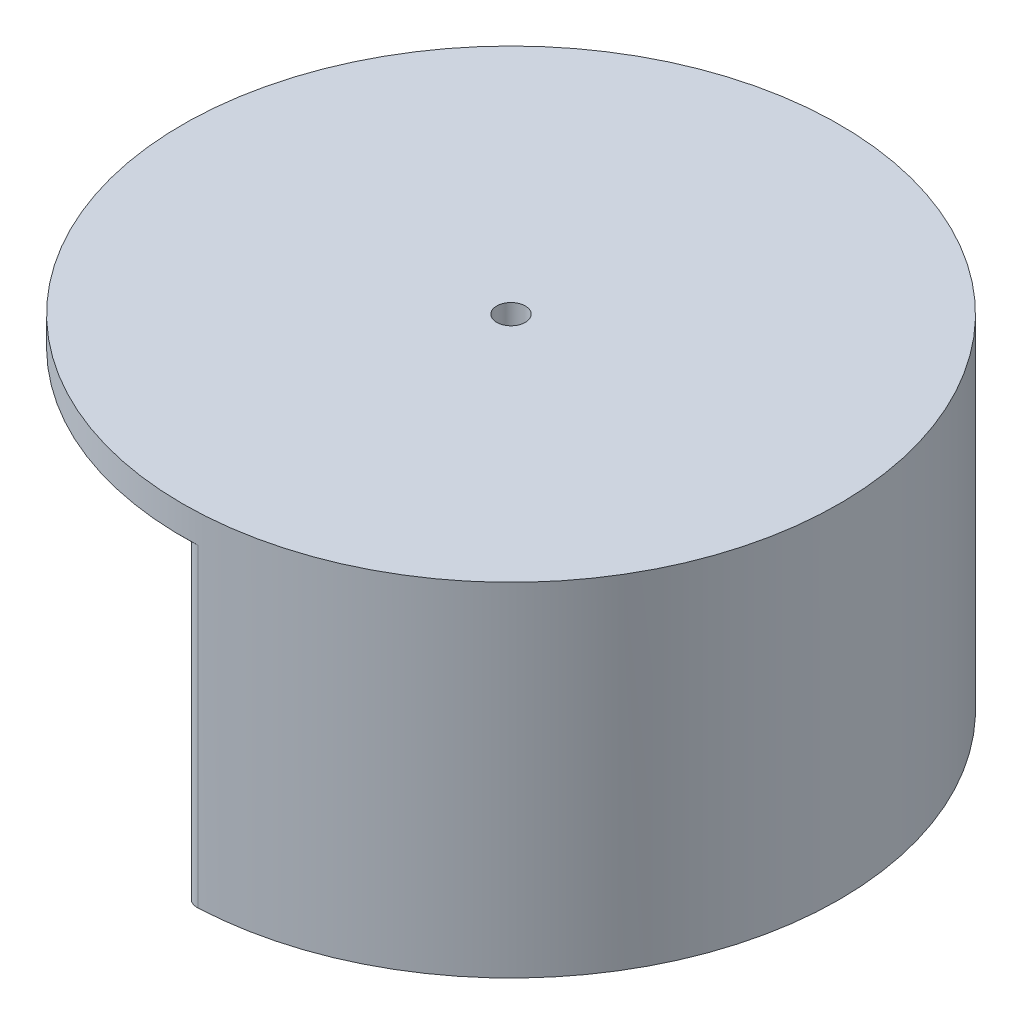
SolidWorks part; units mm, degrees
ref_plane "Front Plane" through (0, 0, 0) normal (0, 0, 1) x (1, 0, 0)
ref_plane "Top Plane" through (0, 0, 0) normal (0, 1, 0) x (1, 0, 0)
ref_plane "Right Plane" through (0, 0, 0) normal (1, 0, 0) x (0, 0, -1)
sketch "Sketch1" plane through (0, 0, 0) normal (0, 1, 0) x (1, 0, 0)
  circle A0 centre (0, 0) radius 23
  dimension "D1" = 46
extrude "Boss-Extrude1" add sketch "Sketch1" along normal blind 24
sketch "Sketch3" plane through (0, 0, 0) normal (1, 0, 0) x (0, 0, -1)
  line L0 (0, 0.5522) -> (-23, 22)
  line L3 (-23, 22) -> (0, 22) construction
  line L4 (0, 22) -> (0, 0.5522) construction
  line L6 (-23, 24) -> (-23, 0) construction
  line L7 (0, 0) -> (0, 24) construction
  line L8 (-23, 0) -> (23, 0) construction
  line L9 (23, 24) -> (-23, 24) construction
  line L10 (-23, 22) -> (-23, 0)
  line L11 (-23, 0) -> (0, 0)
  line L12 (0, 0) -> (0, 0.5522)
  dimension "D1" = 43
  dimension "D2" = 2
revolve "Cut-Revolve1" cut sketch "Sketch3" angle 180 about L4
sketch "Sketch4" plane through (0, 0, 0) normal (0, -1, 0) x (1, 0, 0)
  line L2 (2, 20.9045) -> (2, -20.9045)
  line L3 (2, 20.9045) -> (2, -20.9045)
  arc A2 (2, -20.9045) -> (2, 20.9045) centre (0, 0) ccw
  arc A3 (2, -20.9045) -> (2, 20.9045) centre (0, 0) ccw
  dimension "D1" = 2
extrude "Cut-Extrude2" cut sketch "Sketch4" against normal offset from surface (22 mm away) 2 up to face at (0, 24, 23)
sketch "Sketch5" plane through (0, 24, 0) normal (0, 1, 0) x (1, 0, 0)
  circle A0 centre (0, 0) radius 1
  dimension "D1" = 2
extrude "Cut-Extrude3" cut sketch "Sketch5" against normal through all
fillet "Fillet1" radius 1 6 edges at (0, 0.7423, -1) (0, 0.7423, 1) (1, 0, 0) (-1, 1.4847, 0) (0, 11, 23) (0, 11, -23)
